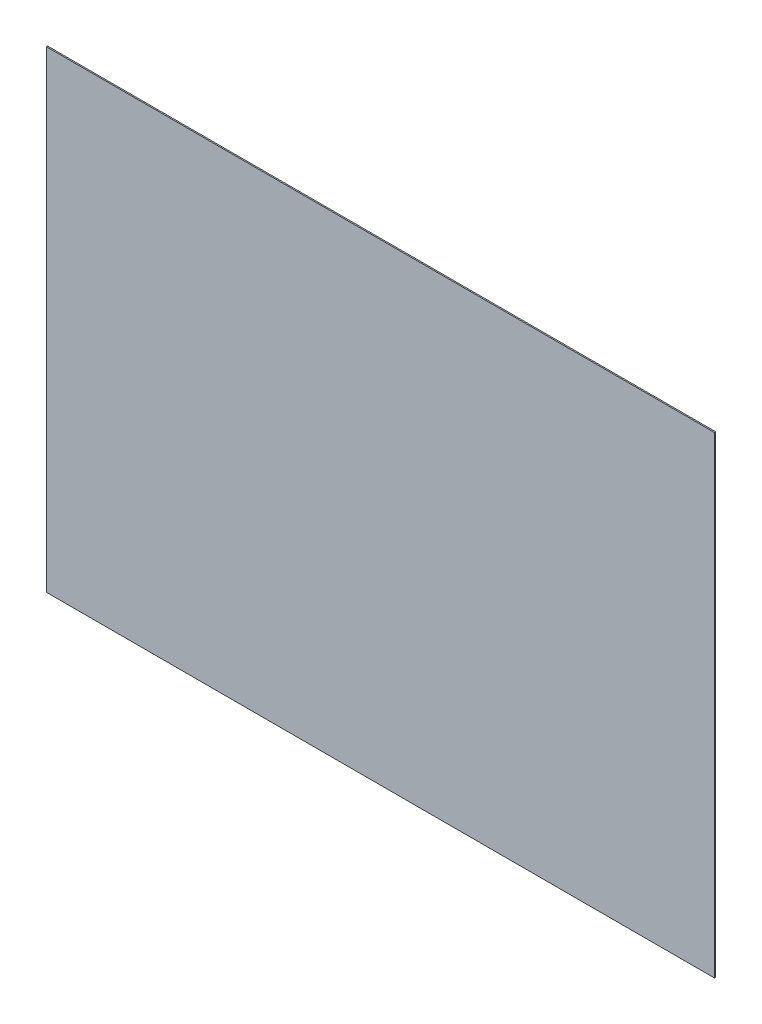
SolidWorks part; units mm, degrees
ref_plane "Plano frontal" through (0, 0, 0) normal (0, 0, 1) x (1, 0, 0)
ref_plane "Plano superior" through (0, 0, 0) normal (0, 1, 0) x (1, 0, 0)
ref_plane "Plano direito" through (0, 0, 0) normal (1, 0, 0) x (0, 0, -1)
sketch "Esboço1" plane through (0, 0, 0) normal (0, 0, 1) x (1, 0, 0)
  line L1 (-210, -148.5) -> (210, -148.5)
  line L2 (-210, -148.5) -> (-210, 148.5)
  line L3 (-210, 148.5) -> (210, 148.5)
  line L4 (210, -148.5) -> (210, 148.5)
  line L5 (-210, -148.5) -> (210, 148.5) construction
  line L6 (-210, 148.5) -> (210, -148.5) construction
  point P0 (0, 0)
  dimension "D1" = 297
  dimension "D2" = 420
base flange "Flange-base1" sketch "Esboço1" thickness 0.77 reverse thickness direction no parameters "D1"=1
sketch "Curva-Linhas1" [suppressed] plane through (0, 0, 0) normal (0, 1, 0) x (1, 0, 0)
sketch "Caixa delimitadora1" [suppressed] plane through (0, 0, 0) normal (0, 1, 0) x (1, 0, 0)
sheet metal parameters "Chapa metálica1" thickness 0.77 parameters "D1"=1
flat pattern "Padrão-Plano1" [suppressed]
sketch "Curva-Linhas2" plane through (0, 0, 0) normal (0, 1, 0) x (1, 0, 0)
sketch3d "Caixa delimitadora2" [suppressed]
  line L0 (210, -148.5, 0) -> (-210, -148.5, 0) construction
  line L1 (210, 148.5, 0) -> (-210, 148.5, 0) construction
  line L2 (210, -148.5, 0) -> (210, 148.5, 0) construction
  line L3 (-210, -148.5, 0) -> (-210, 148.5, 0) construction
